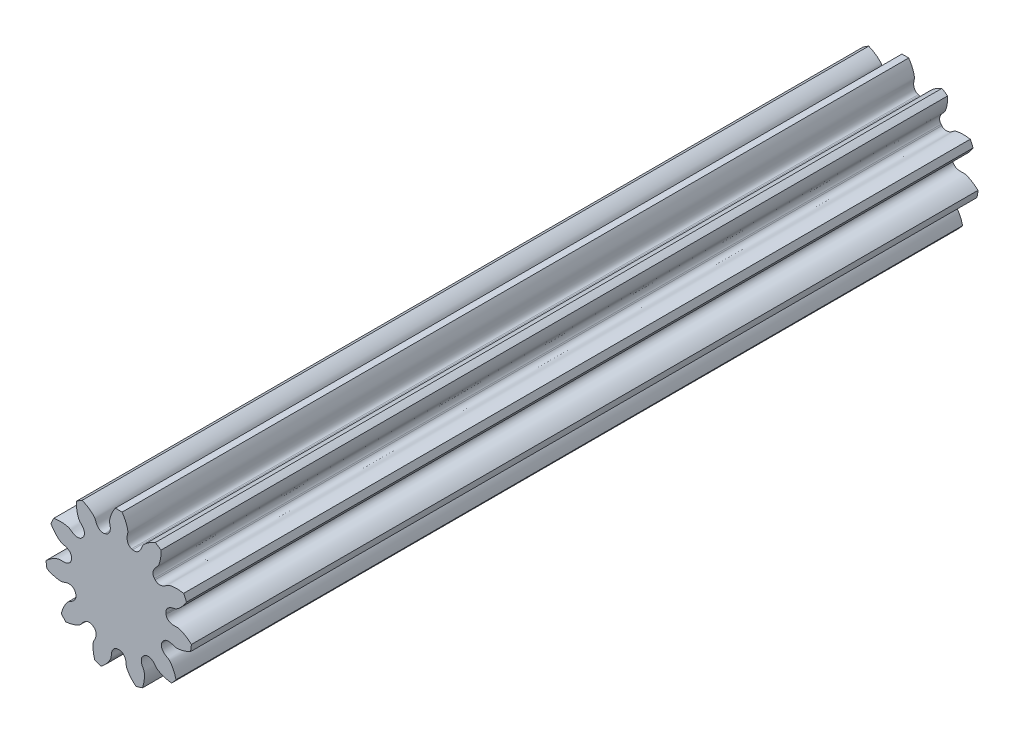
SolidWorks part; units mm, degrees
ref_plane "Спереди" through (0, 0, 0) normal (0, 0, 1) x (1, 0, 0)
ref_plane "Сверху" through (0, 0, 0) normal (0, 1, 0) x (1, 0, 0)
ref_plane "Справа" through (0, 0, 0) normal (1, 0, 0) x (0, 0, -1)
other "Configuration Table"
sketch "Эскиз1" plane through (0, 0, 0) normal (0, 0, 1) x (1, 0, 0)
  line L0 (0, 4.2505) -> (0, 6.5001) construction
  arc A6 (0.303, 6.493) -> (-0.303, 6.493) centre (0, 0) ccw
  arc A8 (3.7653, 5.2984) -> (3.2555, 5.6261) centre (0, 0) ccw
  arc A9 (6.0321, 2.4217) -> (5.7804, 2.9729) centre (0, 0) ccw
  arc A10 (6.3838, -1.224) -> (6.47, -0.6241) centre (0, 0) ccw
  arc A11 (4.7087, -4.481) -> (5.1055, -4.023) centre (0, 0) ccw
  arc A12 (1.5386, -6.3154) -> (2.12, -6.1446) centre (0, 0) ccw
  arc A13 (-2.12, -6.1446) -> (-1.5386, -6.3154) centre (0, 0) ccw
  arc A14 (-5.1055, -4.023) -> (-4.7087, -4.481) centre (0, 0) ccw
  arc A15 (-6.47, -0.6241) -> (-6.3838, -1.224) centre (0, 0) ccw
  arc A16 (-5.7804, 2.9729) -> (-6.0321, 2.4217) centre (0, 0) ccw
  arc A17 (-3.2555, 5.6261) -> (-3.7653, 5.2984) centre (0, 0) ccw
  arc A18 (-4.1999, 0.6538) -> (-4.214, 0.5559) centre (0, 0) ccw
  arc A19 (-3.1797, 2.8207) -> (-3.2445, 2.746) centre (0, 0) ccw
  arc A20 (-1.15, 4.092) -> (-1.2449, 4.0641) centre (0, 0) ccw
  arc A21 (1.2449, 4.0641) -> (1.15, 4.092) centre (0, 0) ccw
  arc A22 (3.2445, 2.746) -> (3.1797, 2.8207) centre (0, 0) ccw
  arc A23 (4.214, 0.5559) -> (4.1999, 0.6538) centre (0, 0) ccw
  arc A24 (3.8456, -1.8106) -> (3.8867, -1.7206) centre (0, 0) ccw
  arc A25 (2.2563, -3.6023) -> (2.3394, -3.5488) centre (0, 0) ccw
  arc A26 (-0.0494, -4.2502) -> (0.0494, -4.2502) centre (0, 0) ccw
  arc A27 (-2.3394, -3.5488) -> (-2.2563, -3.6023) centre (0, 0) ccw
  arc A28 (-3.8867, -1.7206) -> (-3.8456, -1.8106) centre (0, 0) ccw
  spline S0 degree 3 poles (0.303, 6.493) (0.3466, 6.4296) (0.4149, 6.3229) (0.5038, 6.1711) (0.5716, 6.0406) (0.6313, 5.9095) (0.6852, 5.7791) (0.7296, 5.6484) (0.7674, 5.5183) (0.798, 5.3728) (0.8278, 5.1961) (0.7682, 4.9723) (0.7367, 4.7556) (0.754, 4.5684) (0.7852, 4.4471) (0.829, 4.3517) (0.8776, 4.2755) (0.9328, 4.2146) (1.0177, 4.1438) (1.0937, 4.1064) (1.15, 4.092) knots 0 0 0 0 0.085617 0.14097 0.195721 0.24917 0.301247 0.352629 0.402768 0.451734 0.518548 0.599046 0.705842 0.760988 0.807057 0.844573 0.877292 0.907236 0.935686 1 1 1 1
  spline S1 degree 3 poles (-0.303, 6.493) (-0.3466, 6.4296) (-0.4149, 6.3229) (-0.5038, 6.1711) (-0.5716, 6.0406) (-0.6313, 5.9095) (-0.6852, 5.7791) (-0.7296, 5.6484) (-0.7674, 5.5183) (-0.798, 5.3728) (-0.8278, 5.1961) (-0.7682, 4.9723) (-0.7367, 4.7556) (-0.754, 4.5684) (-0.7852, 4.4471) (-0.829, 4.3517) (-0.8776, 4.2755) (-0.9328, 4.2146) (-1.0177, 4.1438) (-1.0937, 4.1064) (-1.15, 4.092) knots 0 0 0 0 0.085617 0.14097 0.195721 0.24917 0.301247 0.352629 0.402768 0.451734 0.518548 0.599046 0.705842 0.760988 0.807057 0.844573 0.877292 0.907236 0.935686 1 1 1 1
  spline S2 degree 3 poles (3.2555, 5.6261) (3.1845, 5.5963) (3.0694, 5.5435) (2.9125, 5.4638) (2.7849, 5.3907) (2.6639, 5.3126) (2.548, 5.2321) (2.4399, 5.1462) (2.3379, 5.0572) (2.2335, 4.9513) (2.1128, 4.8187) (2.042, 4.5983) (1.9513, 4.399) (1.8356, 4.2508) (1.7437, 4.1657) (1.6553, 4.1091) (1.5733, 4.0713) (1.4939, 4.0498) (1.3841, 4.0362) (1.3, 4.0458) (1.2449, 4.0641) knots 0 0 0 0 0.085617 0.14097 0.195721 0.24917 0.301247 0.352629 0.402768 0.451734 0.518548 0.599046 0.705842 0.760988 0.807057 0.844573 0.877292 0.907236 0.935686 1 1 1 1
  spline S3 degree 3 poles (3.7653, 5.2984) (3.7677, 5.2215) (3.7674, 5.0948) (3.7602, 4.9191) (3.7467, 4.7726) (3.7259, 4.6301) (3.7008, 4.4913) (3.6676, 4.3573) (3.629, 4.2274) (3.5761, 4.0885) (3.5056, 3.9237) (3.3345, 3.7676) (3.1908, 3.6024) (3.1041, 3.4356) (3.0649, 3.3166) (3.0502, 3.2127) (3.0498, 3.1224) (3.0633, 3.0412) (3.0965, 2.9357) (3.1402, 2.8632) (3.1797, 2.8207) knots 0 0 0 0 0.085617 0.14097 0.195721 0.24917 0.301247 0.352629 0.402768 0.451734 0.518548 0.599046 0.705842 0.760988 0.807057 0.844573 0.877292 0.907236 0.935686 1 1 1 1
  spline S4 degree 3 poles (5.7804, 2.9729) (5.7046, 2.9862) (5.5791, 3.004) (5.4041, 3.0219) (5.2573, 3.0293) (5.1132, 3.0291) (4.9722, 3.024) (4.8349, 3.0101) (4.7009, 2.9904) (4.5558, 2.9578) (4.3826, 2.9115) (4.2038, 2.7644) (4.0198, 2.6457) (3.8424, 2.5836) (3.719, 2.5617) (3.6141, 2.5619) (3.5246, 2.5744) (3.4462, 2.5993) (3.3465, 2.6472) (3.281, 2.7007) (3.2445, 2.746) knots 0 0 0 0 0.085617 0.14097 0.195721 0.24917 0.301247 0.352629 0.402768 0.451734 0.518548 0.599046 0.705842 0.760988 0.807057 0.844573 0.877292 0.907236 0.935686 1 1 1 1
  spline S5 degree 3 poles (6.0321, 2.4217) (5.9925, 2.3557) (5.9238, 2.2492) (5.8227, 2.1053) (5.7322, 1.9894) (5.6377, 1.8807) (5.5415, 1.7775) (5.4411, 1.6827) (5.3384, 1.5943) (5.2188, 1.5061) (5.0704, 1.4055) (4.8421, 1.3668) (4.6319, 1.3054) (4.4688, 1.212) (4.3714, 1.1331) (4.3029, 1.0537) (4.2537, 0.9778) (4.2212, 0.9023) (4.1921, 0.7956) (4.1897, 0.711) (4.1999, 0.6538) knots 0 0 0 0 0.085617 0.14097 0.195721 0.24917 0.301247 0.352629 0.402768 0.451734 0.518548 0.599046 0.705842 0.760988 0.807057 0.844573 0.877292 0.907236 0.935686 1 1 1 1
  spline S6 degree 3 poles (6.47, -0.6241) (6.4135, -0.572) (6.3176, -0.4892) (6.18, -0.3795) (6.0605, -0.2938) (5.9391, -0.2162) (5.8178, -0.1442) (5.6948, -0.0816) (5.5714, -0.0258) (5.4317, 0.0252) (5.261, 0.0799) (5.031, 0.0528) (4.812, 0.0524) (4.6292, 0.0961) (4.5136, 0.1444) (4.4254, 0.2013) (4.3569, 0.2602) (4.3044, 0.3235) (4.2465, 0.4177) (4.2203, 0.4982) (4.214, 0.5559) knots 0 0 0 0 0.085617 0.14097 0.195721 0.24917 0.301247 0.352629 0.402768 0.451734 0.518548 0.599046 0.705842 0.760988 0.807057 0.844573 0.877292 0.907236 0.935686 1 1 1 1
  spline S7 degree 3 poles (6.3838, -1.224) (6.3148, -1.2581) (6.1995, -1.3105) (6.0366, -1.3769) (5.8978, -1.4255) (5.7595, -1.4658) (5.6228, -1.5007) (5.4871, -1.5261) (5.3529, -1.5449) (5.2046, -1.5545) (5.0254, -1.5588) (4.8124, -1.468) (4.6023, -1.406) (4.4146, -1.3964) (4.2901, -1.4101) (4.1895, -1.4399) (4.1071, -1.4771) (4.0389, -1.5231) (3.9568, -1.5971) (3.909, -1.667) (3.8867, -1.7206) knots 0 0 0 0 0.085617 0.14097 0.195721 0.24917 0.301247 0.352629 0.402768 0.451734 0.518548 0.599046 0.705842 0.760988 0.807057 0.844573 0.877292 0.907236 0.935686 1 1 1 1
  spline S8 degree 3 poles (5.1055, -4.023) (5.0861, -3.9486) (5.0502, -3.827) (4.9937, -3.6604) (4.9395, -3.5237) (4.8795, -3.3928) (4.8163, -3.2667) (4.7466, -3.1475) (4.673, -3.0338) (4.5831, -2.9154) (4.469, -2.7771) (4.2609, -2.6756) (4.0765, -2.5575) (3.9463, -2.4219) (3.8751, -2.3188) (3.8317, -2.2233) (3.8059, -2.1366) (3.796, -2.055) (3.7981, -1.9445) (3.8196, -1.8626) (3.8456, -1.8106) knots 0 0 0 0 0.085617 0.14097 0.195721 0.24917 0.301247 0.352629 0.402768 0.451734 0.518548 0.599046 0.705842 0.760988 0.807057 0.844573 0.877292 0.907236 0.935686 1 1 1 1
  spline S9 degree 3 poles (4.7087, -4.481) (4.6322, -4.4724) (4.5068, -4.4542) (4.3339, -4.422) (4.1908, -4.3878) (4.0527, -4.3469) (3.9189, -4.3023) (3.791, -4.2503) (3.6679, -4.1937) (3.538, -4.1215) (3.3848, -4.0283) (3.2547, -3.8367) (3.1116, -3.671) (2.9588, -3.5615) (2.8467, -3.5057) (2.7459, -3.4763) (2.6565, -3.4631) (2.5743, -3.4649) (2.4652, -3.4828) (2.3872, -3.5157) (2.3394, -3.5488) knots 0 0 0 0 0.085617 0.14097 0.195721 0.24917 0.301247 0.352629 0.402768 0.451734 0.518548 0.599046 0.705842 0.760988 0.807057 0.844573 0.877292 0.907236 0.935686 1 1 1 1
  spline S10 degree 3 poles (2.12, -6.1446) (2.144, -6.0715) (2.1795, -5.9499) (2.222, -5.7792) (2.2503, -5.6349) (2.2706, -5.4922) (2.2856, -5.352) (2.2914, -5.214) (2.291, -5.0786) (2.2793, -4.9304) (2.2582, -4.7524) (2.138, -4.5545) (2.0467, -4.3554) (2.0105, -4.1709) (2.0063, -4.0457) (2.0215, -3.9419) (2.0466, -3.8551) (2.0824, -3.7811) (2.144, -3.6892) (2.2063, -3.6319) (2.2563, -3.6023) knots 0 0 0 0 0.085617 0.14097 0.195721 0.24917 0.301247 0.352629 0.402768 0.451734 0.518548 0.599046 0.705842 0.760988 0.807057 0.844573 0.877292 0.907236 0.935686 1 1 1 1
  spline S11 degree 3 poles (1.5386, -6.3154) (1.4789, -6.2668) (1.3833, -6.1836) (1.2552, -6.0631) (1.1533, -5.957) (1.0592, -5.8479) (0.9707, -5.738) (0.8913, -5.6252) (0.8184, -5.511) (0.7481, -5.38) (0.6696, -5.2188) (0.6638, -4.9873) (0.6329, -4.7705) (0.5636, -4.5958) (0.4995, -4.4882) (0.4306, -4.409) (0.3625, -4.3496) (0.2924, -4.3067) (0.1909, -4.2627) (0.1075, -4.2482) (0.0494, -4.2502) knots 0 0 0 0 0.085617 0.14097 0.195721 0.24917 0.301247 0.352629 0.402768 0.451734 0.518548 0.599046 0.705842 0.760988 0.807057 0.844573 0.877292 0.907236 0.935686 1 1 1 1
  spline S12 degree 3 poles (-1.5386, -6.3154) (-1.4789, -6.2668) (-1.3833, -6.1836) (-1.2552, -6.0631) (-1.1533, -5.957) (-1.0592, -5.8479) (-0.9707, -5.738) (-0.8913, -5.6252) (-0.8184, -5.511) (-0.7481, -5.38) (-0.6696, -5.2188) (-0.6638, -4.9873) (-0.6329, -4.7705) (-0.5636, -4.5958) (-0.4995, -4.4882) (-0.4306, -4.409) (-0.3625, -4.3496) (-0.2924, -4.3067) (-0.1909, -4.2627) (-0.1075, -4.2482) (-0.0494, -4.2502) knots 0 0 0 0 0.085617 0.14097 0.195721 0.24917 0.301247 0.352629 0.402768 0.451734 0.518548 0.599046 0.705842 0.760988 0.807057 0.844573 0.877292 0.907236 0.935686 1 1 1 1
  spline S13 degree 3 poles (-2.12, -6.1446) (-2.144, -6.0715) (-2.1795, -5.9499) (-2.222, -5.7792) (-2.2503, -5.6349) (-2.2706, -5.4922) (-2.2856, -5.352) (-2.2914, -5.214) (-2.291, -5.0786) (-2.2793, -4.9304) (-2.2582, -4.7524) (-2.138, -4.5545) (-2.0467, -4.3554) (-2.0105, -4.1709) (-2.0063, -4.0457) (-2.0215, -3.9419) (-2.0466, -3.8551) (-2.0824, -3.7811) (-2.144, -3.6892) (-2.2063, -3.6319) (-2.2563, -3.6023) knots 0 0 0 0 0.085617 0.14097 0.195721 0.24917 0.301247 0.352629 0.402768 0.451734 0.518548 0.599046 0.705842 0.760988 0.807057 0.844573 0.877292 0.907236 0.935686 1 1 1 1
  spline S14 degree 3 poles (-4.7087, -4.481) (-4.6322, -4.4724) (-4.5068, -4.4542) (-4.3339, -4.422) (-4.1908, -4.3878) (-4.0527, -4.3469) (-3.9189, -4.3023) (-3.791, -4.2503) (-3.6679, -4.1937) (-3.538, -4.1215) (-3.3848, -4.0283) (-3.2547, -3.8367) (-3.1116, -3.671) (-2.9588, -3.5615) (-2.8467, -3.5057) (-2.7459, -3.4763) (-2.6565, -3.4631) (-2.5743, -3.4649) (-2.4652, -3.4828) (-2.3872, -3.5157) (-2.3394, -3.5488) knots 0 0 0 0 0.085617 0.14097 0.195721 0.24917 0.301247 0.352629 0.402768 0.451734 0.518548 0.599046 0.705842 0.760988 0.807057 0.844573 0.877292 0.907236 0.935686 1 1 1 1
  spline S15 degree 3 poles (-5.1055, -4.023) (-5.0861, -3.9486) (-5.0502, -3.827) (-4.9937, -3.6604) (-4.9395, -3.5237) (-4.8795, -3.3928) (-4.8163, -3.2667) (-4.7466, -3.1475) (-4.673, -3.0338) (-4.5831, -2.9154) (-4.469, -2.7771) (-4.2609, -2.6756) (-4.0765, -2.5575) (-3.9463, -2.4219) (-3.8751, -2.3188) (-3.8317, -2.2233) (-3.8059, -2.1366) (-3.796, -2.055) (-3.7981, -1.9445) (-3.8196, -1.8626) (-3.8456, -1.8106) knots 0 0 0 0 0.085617 0.14097 0.195721 0.24917 0.301247 0.352629 0.402768 0.451734 0.518548 0.599046 0.705842 0.760988 0.807057 0.844573 0.877292 0.907236 0.935686 1 1 1 1
  spline S16 degree 3 poles (-6.3838, -1.224) (-6.3148, -1.2581) (-6.1995, -1.3105) (-6.0366, -1.3769) (-5.8978, -1.4255) (-5.7595, -1.4658) (-5.6228, -1.5007) (-5.4871, -1.5261) (-5.3529, -1.5449) (-5.2046, -1.5545) (-5.0254, -1.5588) (-4.8124, -1.468) (-4.6023, -1.406) (-4.4146, -1.3964) (-4.2901, -1.4101) (-4.1895, -1.4399) (-4.1071, -1.4771) (-4.0389, -1.5231) (-3.9568, -1.5971) (-3.909, -1.667) (-3.8867, -1.7206) knots 0 0 0 0 0.085617 0.14097 0.195721 0.24917 0.301247 0.352629 0.402768 0.451734 0.518548 0.599046 0.705842 0.760988 0.807057 0.844573 0.877292 0.907236 0.935686 1 1 1 1
  spline S17 degree 3 poles (-6.47, -0.6241) (-6.4135, -0.572) (-6.3176, -0.4892) (-6.18, -0.3795) (-6.0605, -0.2938) (-5.9391, -0.2162) (-5.8178, -0.1442) (-5.6948, -0.0816) (-5.5714, -0.0258) (-5.4317, 0.0252) (-5.261, 0.0799) (-5.031, 0.0528) (-4.812, 0.0524) (-4.6292, 0.0961) (-4.5136, 0.1444) (-4.4254, 0.2013) (-4.3569, 0.2602) (-4.3044, 0.3235) (-4.2465, 0.4177) (-4.2203, 0.4982) (-4.214, 0.5559) knots 0 0 0 0 0.085617 0.14097 0.195721 0.24917 0.301247 0.352629 0.402768 0.451734 0.518548 0.599046 0.705842 0.760988 0.807057 0.844573 0.877292 0.907236 0.935686 1 1 1 1
  spline S18 degree 3 poles (-6.0321, 2.4217) (-5.9925, 2.3557) (-5.9238, 2.2492) (-5.8227, 2.1053) (-5.7322, 1.9894) (-5.6377, 1.8807) (-5.5415, 1.7775) (-5.4411, 1.6827) (-5.3384, 1.5943) (-5.2188, 1.5061) (-5.0704, 1.4055) (-4.8421, 1.3668) (-4.6319, 1.3054) (-4.4688, 1.212) (-4.3714, 1.1331) (-4.3029, 1.0537) (-4.2537, 0.9778) (-4.2212, 0.9023) (-4.1921, 0.7956) (-4.1897, 0.711) (-4.1999, 0.6538) knots 0 0 0 0 0.085617 0.14097 0.195721 0.24917 0.301247 0.352629 0.402768 0.451734 0.518548 0.599046 0.705842 0.760988 0.807057 0.844573 0.877292 0.907236 0.935686 1 1 1 1
  spline S19 degree 3 poles (-5.7804, 2.9729) (-5.7046, 2.9862) (-5.5791, 3.004) (-5.4041, 3.0219) (-5.2573, 3.0293) (-5.1132, 3.0291) (-4.9722, 3.024) (-4.8349, 3.0101) (-4.7009, 2.9904) (-4.5558, 2.9578) (-4.3826, 2.9115) (-4.2038, 2.7644) (-4.0198, 2.6457) (-3.8424, 2.5836) (-3.719, 2.5617) (-3.6141, 2.5619) (-3.5246, 2.5744) (-3.4462, 2.5993) (-3.3465, 2.6472) (-3.281, 2.7007) (-3.2445, 2.746) knots 0 0 0 0 0.085617 0.14097 0.195721 0.24917 0.301247 0.352629 0.402768 0.451734 0.518548 0.599046 0.705842 0.760988 0.807057 0.844573 0.877292 0.907236 0.935686 1 1 1 1
  spline S20 degree 3 poles (-3.7653, 5.2984) (-3.7677, 5.2215) (-3.7674, 5.0948) (-3.7602, 4.9191) (-3.7467, 4.7726) (-3.7259, 4.6301) (-3.7008, 4.4913) (-3.6676, 4.3573) (-3.629, 4.2274) (-3.5761, 4.0885) (-3.5056, 3.9237) (-3.3345, 3.7676) (-3.1908, 3.6024) (-3.1041, 3.4356) (-3.0649, 3.3166) (-3.0502, 3.2127) (-3.0498, 3.1224) (-3.0633, 3.0412) (-3.0965, 2.9357) (-3.1402, 2.8632) (-3.1797, 2.8207) knots 0 0 0 0 0.085617 0.14097 0.195721 0.24917 0.301247 0.352629 0.402768 0.451734 0.518548 0.599046 0.705842 0.760988 0.807057 0.844573 0.877292 0.907236 0.935686 1 1 1 1
  spline S21 degree 3 poles (-3.2555, 5.6261) (-3.1845, 5.5963) (-3.0694, 5.5435) (-2.9125, 5.4638) (-2.7849, 5.3907) (-2.6639, 5.3126) (-2.548, 5.2321) (-2.4399, 5.1462) (-2.3379, 5.0572) (-2.2335, 4.9513) (-2.1128, 4.8187) (-2.042, 4.5983) (-1.9513, 4.399) (-1.8356, 4.2508) (-1.7437, 4.1657) (-1.6553, 4.1091) (-1.5733, 4.0713) (-1.4939, 4.0498) (-1.3841, 4.0362) (-1.3, 4.0458) (-1.2449, 4.0641) knots 0 0 0 0 0.085617 0.14097 0.195721 0.24917 0.301247 0.352629 0.402768 0.451734 0.518548 0.599046 0.705842 0.760988 0.807057 0.844573 0.877292 0.907236 0.935686 1 1 1 1
  point P469 (0, 0)
  point P490 (0, 0)
  dimension "D1" = 11
  dimension "D2" = 11
extrude "Бобышка-Вытянуть1" add sketch "Эскиз1" along normal blind 70
